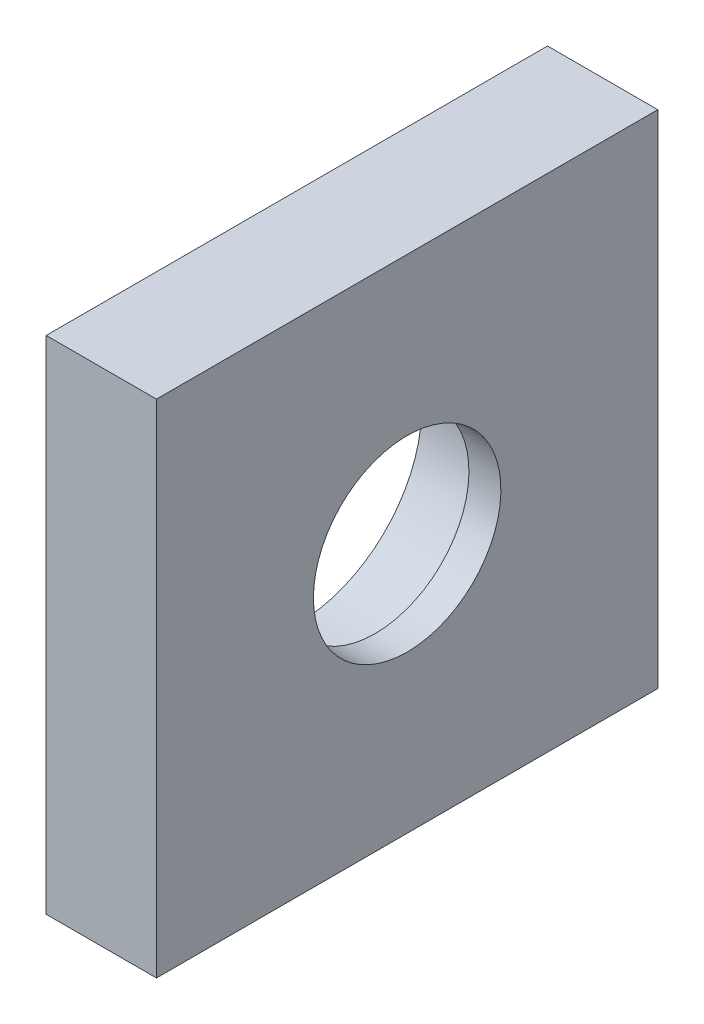
SolidWorks part; units mm, degrees
ref_plane "Front Plane" through (0, 0, 0) normal (0, 0, 1) x (1, 0, 0)
ref_plane "Top Plane" through (0, 0, 0) normal (0, 1, 0) x (1, 0, 0)
ref_plane "Right Plane" through (0, 0, 0) normal (1, 0, 0) x (0, 0, -1)
sketch "Sketch1" plane through (0, 0, 0) normal (0, 0, 1) x (1, 0, 0)
  line L1 (5.9097, -28.7494) -> (11.4977, -28.7494)
  line L2 (5.9097, -28.7494) -> (5.9097, -3.3494)
  line L3 (5.9097, -3.3494) -> (11.4977, -3.3494)
  line L4 (11.4977, -28.7494) -> (11.4977, -3.3494)
  dimension "D1" = 5.588
  dimension "D2" = 25.4
extrude "Boss-Extrude1" add sketch "Sketch1" along normal blind 25.4
sketch "Sketch3" plane through (5.9097, 0, 0) normal (-1, 0, 0) x (0, 0, 1)
  circle A0 centre (12.7, -16.0494) radius 6.35 construction
  circle A1 centre (12.7, -16.0494) radius 6.35
  circle A2 centre (12.7, -16.0494) radius 6.3246
  dimension "D1" = 0.0254
sketch "Sketch4" plane through (5.9097, 0, 0) normal (-1, 0, 0) x (0, 0, 1)
  circle A0 centre (12.7, -16.0494) radius 4.7494 construction
  circle A1 centre (12.7, -16.0494) radius 4.7494
extrude "Cut-Extrude1" cut sketch "Sketch4" against normal up to surface (5.588 mm away) up to face at (11.4977, -16.0494, 12.7)
extrude "Cut-Extrude2" cut sketch "Sketch3" against normal up to surface (3.9688 mm away) contours A2 region at (5.9097, -16.0494, 12.7)
